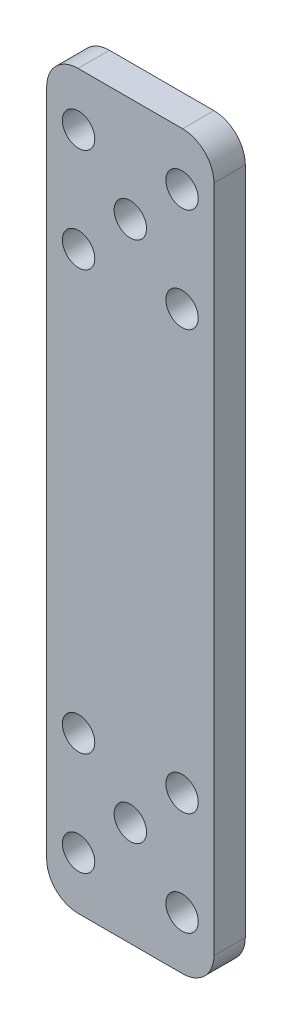
SolidWorks part; units mm, degrees
ref_plane "前视基准面" through (0, 0, 0) normal (0, 0, 1) x (1, 0, 0)
ref_plane "上视基准面" through (0, 0, 0) normal (0, 1, 0) x (1, 0, 0)
ref_plane "右视基准面" through (0, 0, 0) normal (1, 0, 0) x (0, 0, -1)
other "Configuration Table"
sketch "草图1" plane through (0, 0, 0) normal (0, 0, 1) x (1, 0, 0)
  line L0 (0, 60.2122) -> (0, -102.648) construction
  line L1 (-60.5647, 6.2167) -> (61.8958, 6.2167) construction
  line L2 (5, 16.2167) -> (-5, 16.2167)
  line L3 (-8, -66.7833) -> (-4, -108.7833)
  line L4 (0, -24.3301) -> (0, -46.8317) construction
  line L5 (8, -66.7833) -> (4, -108.7833)
  line L6 (-8, 13.2167) -> (-8, -66.7833)
  line L7 (-4, -108.7833) -> (4, -108.7833)
  line L8 (8, 13.2167) -> (8, -66.7833)
  line L12 (-27.2464, -43.7833) -> (27.2464, -43.7833) construction
  circle A0 centre (0, 6.2167) radius 7 construction
  circle A1 centre (-4.9497, 11.1665) radius 1.55
  circle A2 centre (4.9497, 11.1665) radius 1.55
  circle A3 centre (4.9497, 1.267) radius 1.55
  circle A4 centre (-4.9497, 1.267) radius 1.55
  circle A5 centre (0, -43.7833) radius 1.55
  circle A6 centre (0, -43.7833) radius 7 construction
  circle A7 centre (4.9497, -38.8335) radius 1.55
  circle A8 centre (-4.9497, -38.8335) radius 1.55
  arc A9 (8, 13.2167) -> (5, 16.2167) centre (5, 13.2167) ccw
  arc A10 (-8, 13.2167) -> (-5, 16.2167) centre (-5, 13.2167) cw
  circle A11 centre (4.9497, -48.733) radius 1.55
  circle A12 centre (-4.9497, -48.733) radius 1.55
  circle A13 centre (0, 6.2167) radius 1.55
  point P18 (0, 0)
  point P39 (0, -108.7833)
  point P44 (0, 6.2167)
  point P46 (0, -43.7833)
  dimension "D2" = 14
  dimension "D3" = 3.1
  dimension "D6" = 3.1
  dimension "D7" = 0
  dimension "D14" = 4
  dimension "D15" = 8
  dimension "D16" = 3.1
  dimension "D17" = 80
  dimension "D9" = 3
  dimension "D8" = 3.1
  dimension "D13" = 14
  dimension "D5" = 50
  dimension "D10" = 16
  dimension "D11" = 125
  dimension "D12" = 115
  dimension "D4" = 4
extrude "凸台-拉伸1" add sketch "草图1" along normal blind 3
sketch "草图2" plane through (0, 0, 0) normal (0, 0, -1) x (-1, 0, 0)
  line L0 (-14.1091, -98.7833) -> (16.5699, -98.7833)
  line L1 (16.5699, -98.7833) -> (16.5699, -119.0749)
  line L2 (16.5699, -119.0749) -> (-14.1091, -119.0749)
  line L3 (-14.1091, -119.0749) -> (-14.1091, -98.7833)
  line L4 (4, -108.7833) -> (-4, -108.7833) construction
  dimension "D1" = 10
extrude "切除-拉伸1" cut sketch "草图2" against normal blind 10
sketch "草图3" plane through (0, 0, 0) normal (0, 0, -1) x (-1, 0, 0)
  line L0 (4.9524, -98.7833) -> (-4.9524, -98.7833) construction
  circle A0 centre (0, -83.7833) radius 1
  circle A1 centre (0, -90.7833) radius 1
  circle A2 centre (0, -73.7833) radius 1
  dimension "D3" = 2
  dimension "D1" = 15
  dimension "D2" = 8
  dimension "D4" = 25
extrude "切除-拉伸2" cut sketch "草图3" against normal blind 20
sketch "草图4" plane through (0, 0, 0) normal (0, 0, -1) x (-1, 0, 0)
  line L0 (-8, -66.7833) -> (-8, 13.2167) construction
  line L1 (-8, -53.7833) -> (15.9609, -53.7833)
  line L2 (-8, -53.7833) -> (-8, -106.112)
  line L3 (-8, -106.112) -> (15.9609, -106.112)
  line L4 (15.9609, -53.7833) -> (15.9609, -106.112)
  circle A0 centre (0, -43.7833) radius 1.55 construction
  dimension "D1" = 10
extrude "切除-拉伸3" cut sketch "草图4" against normal blind 10
fillet "圆角1" radius 3 2 edges at (-8, -53.7833, 1.5) (8, -53.7833, 1.5)
